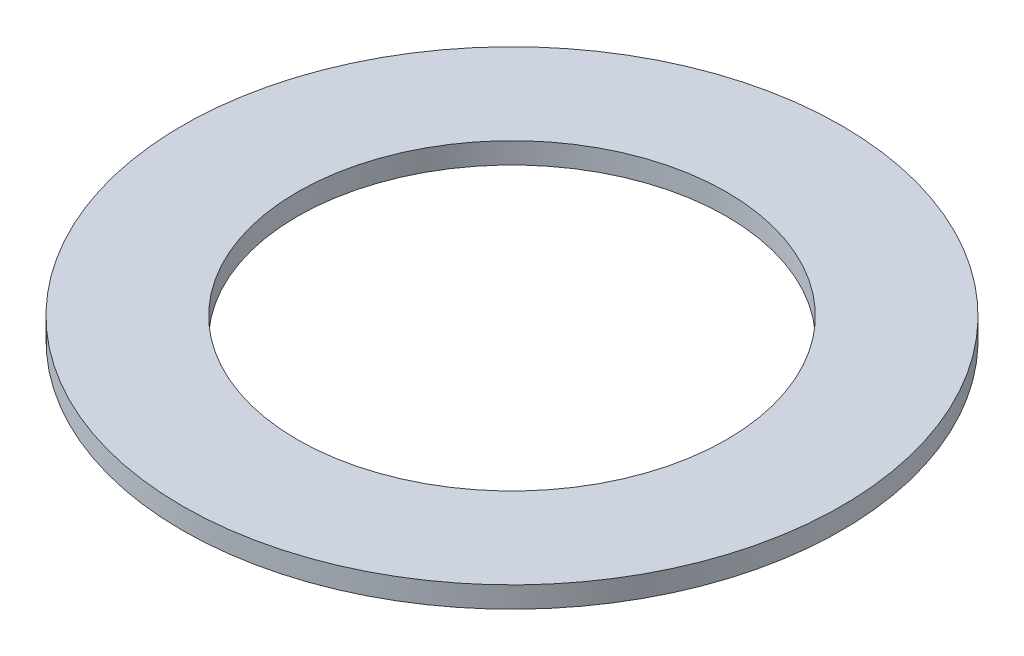
SolidWorks part; units mm, degrees
ref_plane "Front" through (0, 0, 0) normal (0, 0, 1) x (1, 0, 0)
ref_plane "Top" through (0, 0, 0) normal (0, 1, 0) x (1, 0, 0)
ref_plane "Right" through (0, 0, 0) normal (1, 0, 0) x (0, 0, -1)
ref_plane "Plane1" through (0, 0, 0) normal (0, 0, -1) x (-1, 0, 0)
sketch "Sketch1" plane through (0, 0, 0) normal (0, 0, -1) x (-1, 0, 0)
  line L0 (-8.2677, 0.8128) -> (-12.7, 0.8128)
  line L1 (-12.7, 0.8128) -> (-12.7, 0)
  line L2 (-12.7, 0) -> (-8.2677, 0)
  line L3 (-8.2677, 0) -> (-8.2677, 0.8128)
  line L4 (0, 0) -> (0, 0.8128) construction
revolve "Revolve1" add sketch "Sketch1" angle 360 about L4 reverse direction yes
